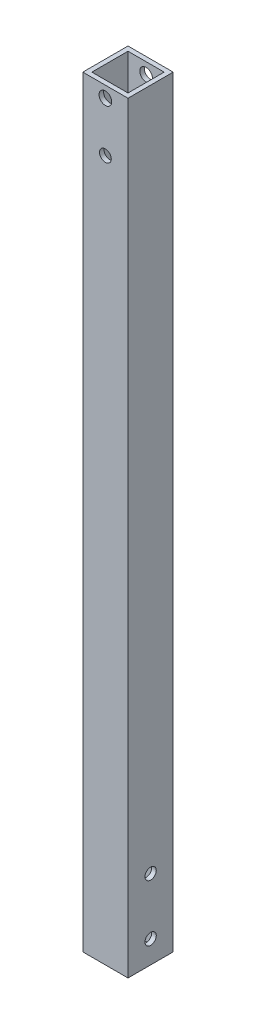
SolidWorks part; units mm, degrees
material "Gerais  - 6061-T6"
ref_plane "Plano frontal" through (0, 0, 0) normal (0, 0, 1) x (1, 0, 0)
ref_plane "Plano superior" through (0, 0, 0) normal (0, 1, 0) x (1, 0, 0)
ref_plane "Plano direito" through (0, 0, 0) normal (1, 0, 0) x (0, 0, -1)
sketch "Esboço1" plane through (0, 0, 0) normal (0, 1, 0) x (1, 0, 0)
  line L1 (0, 0) -> (20, 0)
  line L2 (0, 0) -> (0, 20)
  line L3 (0, 20) -> (20, 20)
  line L4 (20, 0) -> (20, 20)
  dimension "D1" = 20
extrude "Extrusão-Fina1" add sketch "Esboço1" along normal blind 337 thin thin type one direction reverse wall 2
sketch "Esboço2" plane through (0, 0, 0) normal (-1, 0, 0) x (0, 0, 1)
  circle A0 centre (-10, 35) radius 2.5
  circle A1 centre (-10, 10) radius 2.5
extrude "Corte-extrusão1" cut sketch "Esboço2" against normal through all
sketch "Esboço3" plane through (0, 0, -20) normal (0, 0, -1) x (-1, 0, 0)
  circle A2 centre (-10, 310) radius 2.6
  circle A3 centre (-10, 332) radius 2.8
extrude "Corte-extrusão2" cut sketch "Esboço3" against normal through all
